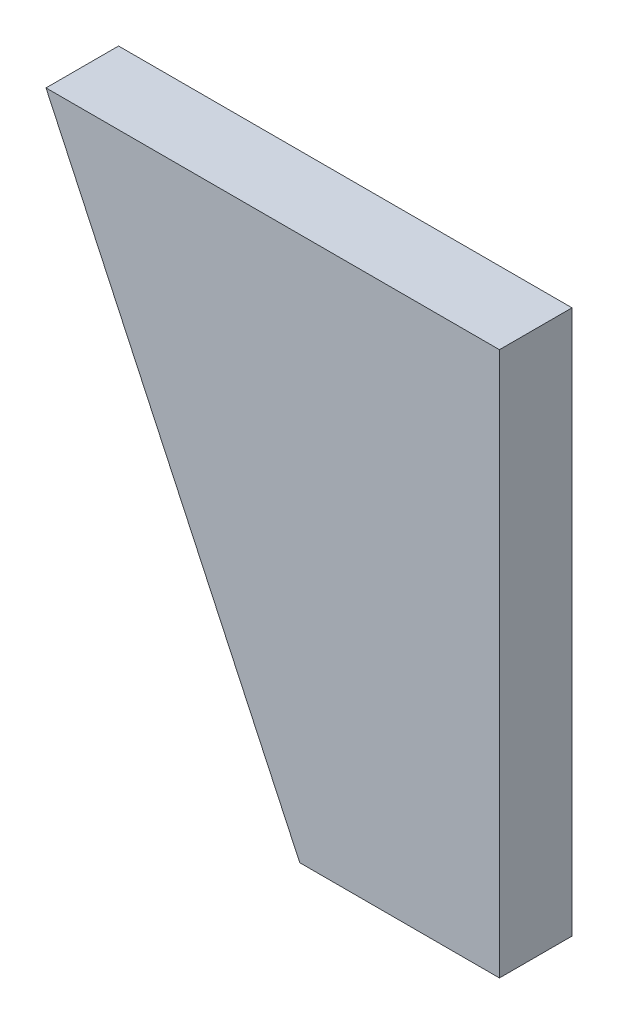
SolidWorks part; units mm, degrees
material "AISI 304"
ref_plane "Спереди" through (0, 0, 0) normal (0, 0, 1) x (1, 0, 0)
ref_plane "Сверху" through (0, 0, 0) normal (0, 1, 0) x (1, 0, 0)
ref_plane "Справа" through (0, 0, 0) normal (1, 0, 0) x (0, 0, -1)
ref_axis "Ось1" through (-62.9241, 0, 0) along (1, 0, 0)
sketch "Эскиз1" plane through (0, 0, 0) normal (0, 0, 1) x (1, 0, 0)
  line L0 (0, 0) -> (53, 0) construction
  line L1 (0, 100) -> (0, 0) construction
  line L2 (0, 102) -> (0.3488, 102)
  line L3 (0, 100) -> (0.3488, 100)
  line L4 (0, 102) -> (0, 100)
  line L5 (51, 0) -> (53, 0)
  line L6 (49.8785, 19.1) -> (51.8921, 19.1)
  arc A0 (0.3488, 102) -> (28.8538, 85.9935) centre (0.3488, 68.6154) cw
  arc A1 (28.8538, 85.9935) -> (53, 0) centre (-112.2, 0) cw
  arc A2 (0.3488, 100) -> (27.1461, 84.9524) centre (0.3488, 68.6154) cw
  arc A3 (27.1461, 84.9524) -> (51, 0) centre (-112.2, 0) cw
  point P0 (0, 101)
  dimension "D3" = 163.2
  dimension "D4" = 31.3846
  dimension "D1" = 204
  dimension "D6" = 38.2
  dimension "D5" = 53
  dimension "D2" = 2
ref_plane "Плоскость1" through (53, 0, 0) normal (1, 0, 0) x (0, 0, -1)
sketch "Эскиз2" plane through (0, 0, 0) normal (0, 0, 1) x (1, 0, 0)
  line L0 (59, 70) -> (53, 70) construction
  line L1 (53, 85) -> (59, 85) construction
  line L2 (53, 85) -> (53, 55)
  line L3 (53, 55) -> (59, 55) construction
  line L4 (59, 85) -> (59, 55) construction
  line L5 (53, 85) -> (28, 85)
  line L6 (0, 100) -> (0, 0) construction
  line L7 (0, 0) -> (53, 0) construction
  line L8 (28, 85) -> (41.9892, 55)
  line L9 (41.9892, 55) -> (53, 55)
  dimension "D1" = 30
  dimension "D2" = 6
  dimension "D3" = 59
  dimension "D4" = 70
  dimension "D5" = 25
  dimension "D6" = 31
extrude "Бобышка-Вытянуть1" add sketch "Эскиз2" along normal mid plane 4 contours L2 L5 L8 L9
equation "\"D\"= 204мм"
equation "\"D1@Эскиз1\"=\"D\""
equation "\"D3@Эскиз1\"=\"D\"*0.8"
equation "\"D4@Эскиз1\"=\"D\"/6.5"
